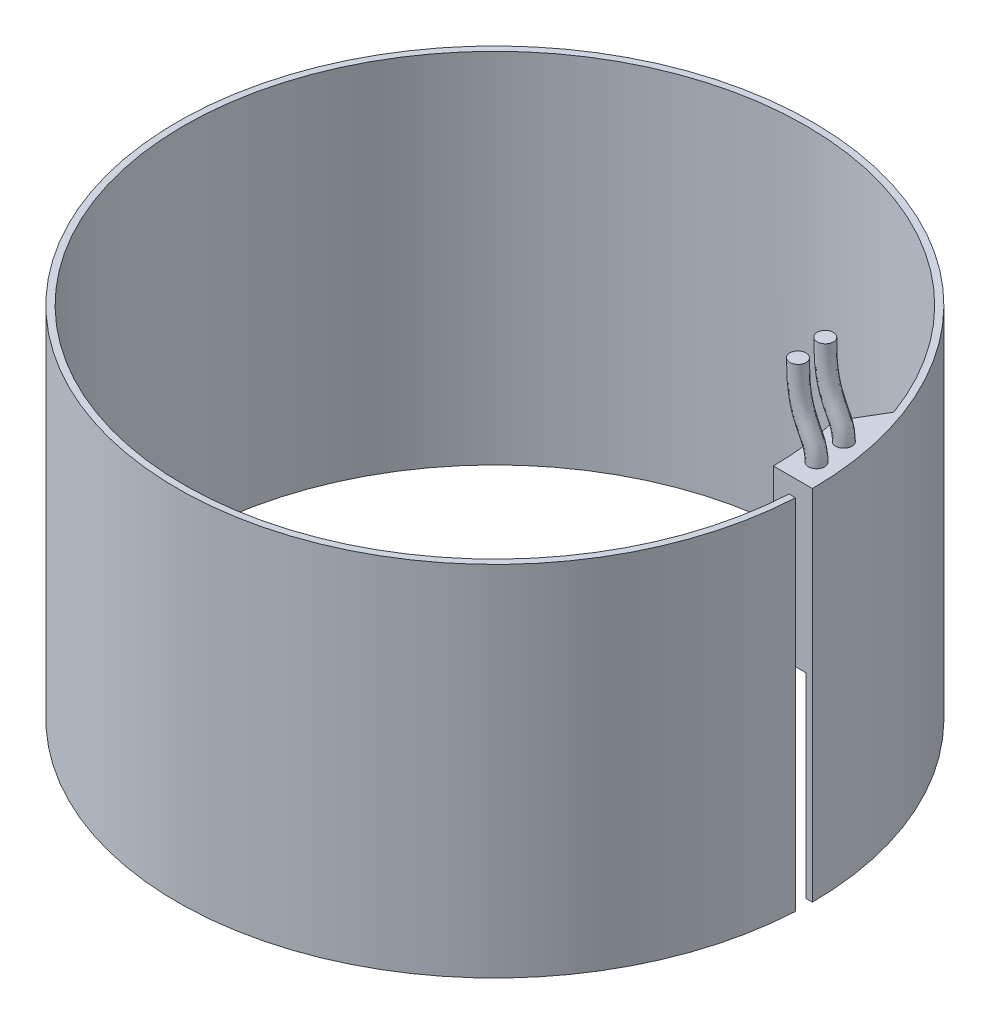
SolidWorks part; units mm, degrees
ref_plane "Front Plane" through (0, 0, 0) normal (0, 0, 1) x (1, 0, 0)
ref_plane "Top Plane" through (0, 0, 0) normal (0, 1, 0) x (1, 0, 0)
ref_plane "Right Plane" through (0, 0, 0) normal (1, 0, 0) x (0, 0, -1)
sketch "Sketch1" plane through (0, 0, 0) normal (0, 1, 0) x (1, 0, 0)
  line L0 (9.55, 0) -> (9.75, 0)
  line L2 (9.5369, -0.4998) -> (9.7366, -0.5103)
  line L3 (0, 0) -> (9.5369, -0.4998) construction
  arc A0 (9.75, 0) -> (9.7366, -0.5103) centre (0, 0) ccw
  arc A1 (9.55, 0) -> (9.5369, -0.4998) centre (0, 0) ccw
  dimension "D1" = 19.5
  dimension "D2" = 0.2
  dimension "D3" = 0.5
extrude "Boss-Extrude1" add sketch "Sketch1" along normal blind 11
sketch "Sketch2" plane through (0, 11, 0) normal (0, 1, 0) x (1, 0, 0)
  line L0 (9.55, 0) -> (8.55, 0)
  line L1 (8.2828, 2.121) -> (9.2515, 2.369)
  line L2 (8.2828, 2.121) -> (0, 0) construction
  arc A0 (9.55, 0) -> (9.5369, -0.4998) centre (0, 0) ccw construction
  arc A1 (9.55, 0) -> (9.2515, 2.369) centre (0, 0) ccw
  arc A2 (8.55, 0) -> (8.2828, 2.121) centre (0, 0) ccw
  arc A3 (8.55, 0) -> (8.5383, -0.4475) centre (0, 0) ccw construction
  arc A4 (9.55, 0) -> (9.5369, -0.4998) centre (0, 0) ccw construction
  dimension "D1" = 1
extrude "Boss-Extrude2" add sketch "Sketch2" against normal blind 5
chamfer "Chamfer1" distance 1 angle 45 1 edges at (9.2515, 8.5, -2.369)
sketch "Sketch3" plane through (0, 11, 0) normal (0, 1, 0) x (1, 0, 0)
  arc A0 (8.55, 0) -> (8.2828, 2.121) centre (0, 0) ccw construction
  circle A1 centre (8.985, 1.7299) radius 0.25
  circle A2 centre (9.1132, 0.7649) radius 0.25
  point P0 (9.1132, 0.7649)
  point P1 (8.985, 1.7299)
  point P9 (8.9583, 1.8634)
  point P10 (9.1033, 0.8745)
  point P11 (9.1132, 0.7649)
  point P12 (9.0455, 0.6591)
  point P13 (8.985, 1.7299)
  point P14 (0, 0)
  point P15 (0, 0)
  dimension "D3" = 0.5
  dimension "D1" = 0.6
  dimension "D2" = 0.5952
ref_axis "Axis1" through (0, 11, 0) along (0, -1, 0)
ref_plane "Plane1" through (0, 0, 0) normal (0.0836, 0, 0.9965) x (0.9965, 0, -0.0836)
ref_plane "Plane2" through (0, 0, 0) normal (0.1891, 0, 0.982) x (0.982, 0, -0.1891)
sketch "Sketch4" plane through (0, 0, 0) normal (0.0836, 0, 0.9965) x (0.9965, 0, -0.0836)
  line L2 (9.4617, 11) -> (-9.55, 11) construction
  line L3 (9.1452, 11.4337) -> (9.1452, 10.5663) construction
  spline S0 degree 3 poles (9.1452, 11) (9.1452, 11.8345) (8.5954, 11.7875) (8.6173, 13.5378) knots 0 0 0 0 1 1 1 1
  point P9 (0, 0)
  point P10 (8.7566, 16.2446)
  point P11 (8.6173, 17.5378)
sweep "Sweep1" add profiles "Sketch3" path "Sketch4"
